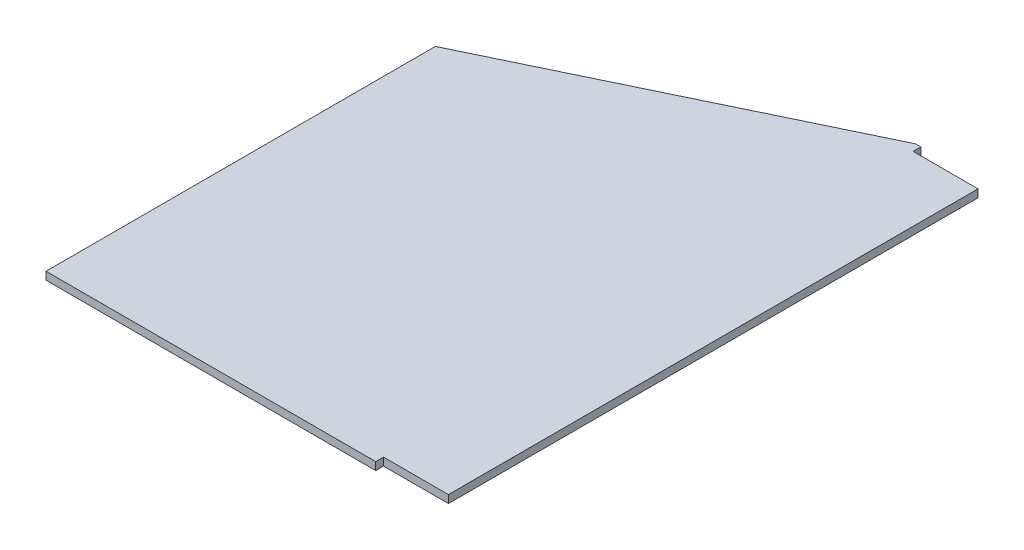
SolidWorks part; units mm, degrees
ref_plane "Front Plane" through (0, 0, 0) normal (0, 0, 1) x (1, 0, 0)
ref_plane "Top Plane" through (0, 0, 0) normal (0, 1, 0) x (1, 0, 0)
ref_plane "Right Plane" through (0, 0, 0) normal (1, 0, 0) x (0, 0, -1)
sketch "Sketch1" plane through (0, 0, 0) normal (0, 1, 0) x (1, 0, 0)
  line L0 (-125, 150) -> (-125, 0)
  line L1 (-125, 0) -> (0, 0)
  line L2 (0, 0) -> (0, 210) construction
  line L3 (0, 210) -> (-125, 150)
  line L15 (0, 0) -> (78.2, 0)
  line L17 (0, 210) -> (78.2, 210)
  line L18 (78.2, 0) -> (78.2, 210)
  dimension "D1" = 210
  dimension "D2" = 150
  dimension "D3" = 125
  dimension "D4" = 78.2
extrude "Boss-Extrude1" add sketch "Sketch1" along normal blind 1.5 and the other way blind 1.5
sketch "Sketch2" plane through (0, 0, -210) normal (0, 0, -1) x (-1, 0, 0)
  line L0 (-78.2, -1.5) -> (-78.2, 1.5) construction
  circle A0 centre (-78.2, 0) radius 51.2
  dimension "D1" = 102.4
extrude "Cut-Extrude1" cut sketch "Sketch2" against normal through all
sketch "Sketch3" plane through (0, 0, -210) normal (0, 0, -1) x (-1, 0, 0)
  line L0 (0, 0) -> (-78.2, 0) construction
  circle A0 centre (-78.2, 0) radius 76.2
  dimension "D2" = 152.4
  dimension "D1" = 78.2
extrude "Cut-Extrude2" cut sketch "Sketch3" against normal blind 3
sketch "Sketch4" plane through (0, 0, 0) normal (0, 0, 1) x (1, 0, 0)
  line L0 (0, 0) -> (78.2, 0) construction
  circle A0 centre (78.2, 0) radius 76.2
  dimension "D2" = 152.4
  dimension "D1" = 78.2
extrude "Cut-Extrude3" cut sketch "Sketch4" against normal blind 3
